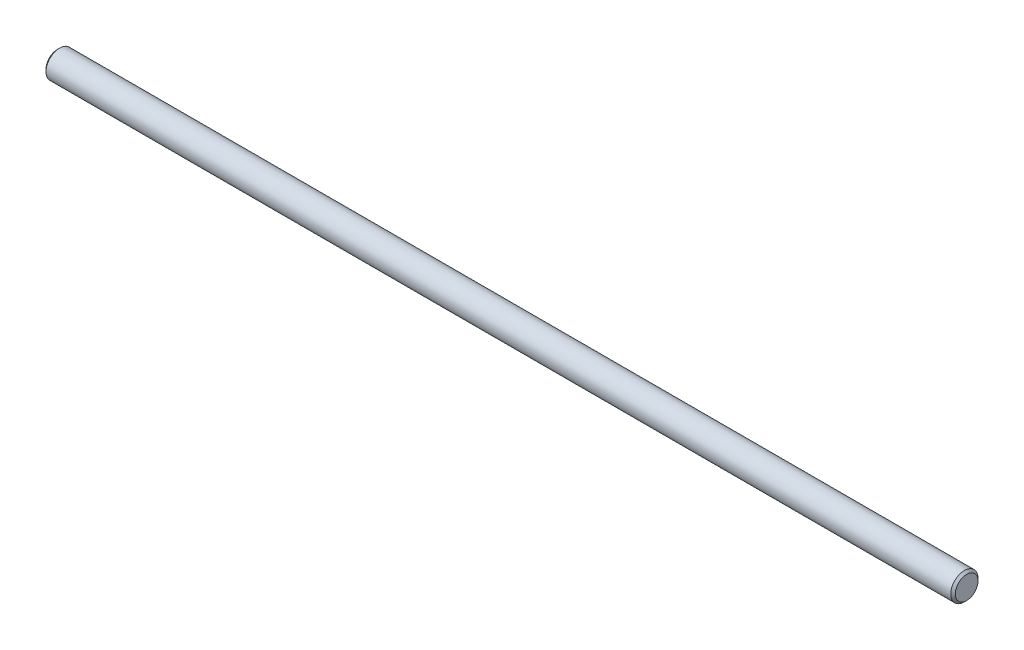
SolidWorks part; units mm, degrees
ref_plane "Front Plane" through (0, 0, 0) normal (0, 0, 1) x (1, 0, 0)
ref_plane "Top Plane" through (0, 0, 0) normal (0, 1, 0) x (1, 0, 0)
ref_plane "Right Plane" through (0, 0, 0) normal (1, 0, 0) x (0, 0, -1)
sketch "Sketch1" plane through (0, 0, 0) normal (0, 0, 1) x (1, 0, 0)
  line L0 (0, 0) -> (200, 0) construction
  line L1 (0, 0) -> (200, 0)
  line L2 (200, 0) -> (200, 3)
  line L3 (200, 3) -> (0, 3)
  line L4 (0, 3) -> (0, 0)
  dimension "L" = 200
  dimension "D" = 6
revolve "Revolve1" add sketch "Sketch1" angle 360 about L0
chamfer "Chamfer1" distance 0.5 angle 45 2 edges at (200, 0, 3) (0, 0, 3)
ref_plane "Plane1" through (0, 0, 3) normal (0, 0, 1) x (1, 0, 0)
ref_plane "Plane2" through (200, 0, 0) normal (1, 0, 0) x (0, 0, -1)
other "DeleteFace1" [suppressed]
chamfer "Chamfer2" [suppressed] distance 2 angle 45
ref_plane "Dim. KC" [suppressed] through (2, 0, 0) normal (1, 0, 0) x (0, 0, -1)
ref_plane "Plane3" [suppressed] through (2, 0, 0) normal (1, 0, 0) x (0, 0, -1)
ref_plane "Plane4" [suppressed] through (8, 0, 0) normal (1, 0, 0) x (0, 0, -1)
sketch "Sketch2" [suppressed] plane through (0, 0, 4) normal (0, 0, 1) x (1, 0, 0)
  line L0 (2, 0) -> (8, 0) construction
  line L1 (2, 1.5) -> (8, 1.5)
  line L2 (2, 1.5) -> (2, -1.5) construction
  line L3 (2, -1.5) -> (8, -1.5)
  line L4 (8, 1.5) -> (8, -1.5) construction
  line L5 (5, 1.5) -> (5, -1.5) construction
  line L6 (2, -4.4) -> (2, 4.4) construction
  line L7 (8, 1.5) -> (8, -1.5)
  line L8 (8, -4.4) -> (8, 4.4) construction
  line L9 (2, 1.5) -> (2, -1.5)
  line L12 (2, -4.4) -> (2, 4.4) construction
  dimension "A" = 6
  dimension "B_s" = 3
extrude "Boss-Extrude1" [suppressed] add sketch "Sketch2" against normal blind 1.8 separate body
fillet "Fillet1" [suppressed] type full round
fillet "Fillet2" [suppressed] type full round
sketch "Sketch3" [suppressed] plane through (0, 0, 4) normal (0, 0, 1) x (1, 0, 0)
  line L0 (9, 1.5) -> (9, -1.5) construction
  line L1 (6.5, 1.5) -> (11.5, 1.5)
  line L2 (6.5, 1.5) -> (6.5, -1.5)
  line L3 (6.5, -1.5) -> (11.5, -1.5)
  line L4 (11.5, 1.5) -> (11.5, -1.5)
  line L7 (6.5, 0) -> (11.5, 0) construction
  line L9 (10, 1.5) -> (10, -1.5) construction
  line L10 (8, 1.5) -> (8, -1.5) construction
  line L11 (2, 1.5) -> (8, 1.5) construction
  line L12 (2, -1.5) -> (8, -1.5) construction
  dimension "D1" = 1.5
  dimension "D2" = 2
  dimension "D3" = 1.5
extrude "Boss-Extrude2" [suppressed] add sketch "Sketch3" against normal blind 1.8
fillet "Fillet3" [suppressed] radius 0.1
other "DeleteFace2" [suppressed]
other "DeleteFace3" [suppressed]
combine bodies "Combine1" [suppressed] operation type subtract main body 101 bodies to subtract 146
ref_plane "KC_SEC1" [suppressed] through (5, 0, 0) normal (1, 0, 0) x (0, 0, -1)
ref_plane "KC_SEC2" [suppressed] through (9, 0, 0) normal (1, 0, 0) x (0, 0, -1)
ref_plane "Dim. WKC" [suppressed] through (2, 0, 0) normal (1, 0, 0) x (0, 0, -1)
ref_plane "Dim. K" [suppressed] through (20, 0, 0) normal (1, 0, 0) x (0, 0, -1)
ref_plane "Plane5" [suppressed] through (2, 0, 0) normal (1, 0, 0) x (0, 0, -1)
ref_plane "Plane6" [suppressed] through (20, 0, 0) normal (1, 0, 0) x (0, 0, -1)
sketch "Sketch4" [suppressed] plane through (0, 0, 4) normal (0, 0, 1) x (1, 0, 0)
  line L0 (2, 1.5) -> (2, -1.5)
  line L1 (2, 1.5) -> (8, 1.5)
  line L2 (2, 1.5) -> (2, -1.5) construction
  line L3 (2, -1.5) -> (8, -1.5)
  line L4 (8, 1.5) -> (8, -1.5)
  line L5 (2, -4.4) -> (2, 4.4) construction
  line L6 (2, -3.3) -> (2, 3.3) construction
  line L7 (8, 0) -> (2, 0) construction
  line L8 (5, 1.5) -> (5, -1.5) construction
  dimension "C" = 6
  dimension "B_s" = 3
extrude "Boss-Extrude3" [suppressed] add sketch "Sketch4" against normal blind 1.8 separate body
sketch "Sketch5" [suppressed] plane through (0, 0, 4) normal (0, 0, 1) x (1, 0, 0)
  line L0 (0, 0) -> (20, 0) construction
  line L2 (20, -3.3) -> (20, 3.3) construction
  line L4 (20, -3.3) -> (20, 3.3) construction
  line L5 (17, 1.5) -> (17, -1.5) construction
  line L9 (14, 1.5) -> (20, 1.5)
  line L10 (14, 1.5) -> (14, -1.5)
  line L11 (14, -1.5) -> (20, -1.5)
  line L12 (20, 1.5) -> (20, -1.5) construction
  line L13 (20, 1.5) -> (20, -1.5)
  dimension "B_s" = 3
  dimension "E" = 6
extrude "Boss-Extrude4" [suppressed] add sketch "Sketch5" against normal blind 1.8 separate body
sketch "Sketch6" [suppressed] plane through (0, 0, 4) normal (0, 0, 1) x (1, 0, 0)
  line L0 (2, 1.5) -> (8, 1.5) construction
  line L1 (6.5, 1.5) -> (11.5, 1.5)
  line L2 (6.5, 1.5) -> (6.5, -1.5)
  line L3 (6.5, -1.5) -> (11.5, -1.5)
  line L4 (11.5, 1.5) -> (11.5, -1.5)
  line L5 (2, -1.5) -> (8, -1.5) construction
  line L6 (8, 1.5) -> (8, -1.5) construction
  line L7 (9, 1.5) -> (9, -1.5) construction
  line L8 (10, 1.5) -> (10, -1.5) construction
  dimension "D1" = 1.5
  dimension "D2" = 2
  dimension "D3" = 1.5
extrude "Boss-Extrude5" [suppressed] add sketch "Sketch6" against normal blind 1.8
fillet "Fillet4" [suppressed] type full round
fillet "Fillet5" [suppressed] type full round
fillet "Fillet6" [suppressed] radius 0.1
fillet "Fillet7" [suppressed] type full round
fillet "Fillet8" [suppressed] type full round
fillet "Fillet9" [suppressed] radius 0.1
other "DeleteFace4" [suppressed]
other "DeleteFace5" [suppressed]
other "DeleteFace6" [suppressed]
other "DeleteFace7" [suppressed]
combine bodies "Combine2" [suppressed] operation type subtract main body 101 bodies to subtract 149 135
ref_plane "WKC_SEC1" [suppressed] through (5, 0, 0) normal (1, 0, 0) x (0, 0, -1)
ref_plane "WKC_SEC2" [suppressed] through (17, 0, 0) normal (1, 0, 0) x (0, 0, -1)
ref_plane "WKC_SEC3" [suppressed] through (9, 0, 0) normal (1, 0, 0) x (0, 0, -1)
ref_plane "Dim. KZ" [suppressed] through (2, 0, 0) normal (1, 0, 0) x (0, 0, -1)
ref_plane "Plane7" [suppressed] through (2, 0, 0) normal (1, 0, 0) x (0, 0, -1)
ref_plane "Plane8" [suppressed] through (8, 0, 0) normal (1, 0, 0) x (0, 0, -1)
sketch "Sketch7" [suppressed] plane through (0, 0, 4) normal (0, 0, 1) x (1, 0, 0)
  line L0 (0, 0) -> (8, 0) construction
  line L1 (2, 1.5) -> (8, 1.5)
  line L2 (2, 1.5) -> (2, -1.5) construction
  line L3 (2, -1.5) -> (8, -1.5)
  line L4 (8, 1.5) -> (8, -1.5) construction
  line L5 (2, -4.4) -> (2, 4.4) construction
  line L6 (2, -4.4) -> (2, 4.4) construction
  line L7 (2, 1.5) -> (2, -1.5)
  line L8 (8, 1.5) -> (8, -1.5)
  line L9 (8, -4.4) -> (8, 4.4) construction
  line L10 (5, 1.5) -> (5, -1.5) construction
  dimension "B_s" = 3
  dimension "Z" = 6
extrude "Boss-Extrude6" [suppressed] add sketch "Sketch7" against normal blind 1.8 separate body
fillet "Fillet10" [suppressed] type full round
fillet "Fillet11" [suppressed] type full round
sketch "Sketch8" [suppressed] plane through (0, 0, 4) normal (0, 0, 1) x (1, 0, 0)
  line L0 (1, 1.5) -> (1, -1.5) construction
  line L1 (-1.5, 1.5) -> (3.5, 1.5)
  line L2 (-1.5, 1.5) -> (-1.5, -1.5)
  line L3 (-1.5, -1.5) -> (3.5, -1.5)
  line L4 (3.5, 1.5) -> (3.5, -1.5)
  line L5 (2, 1.5) -> (2, -1.5) construction
  line L7 (-1.5, 0) -> (3.5, 0) construction
  line L9 (0, 1.5) -> (0, -1.5) construction
  line L10 (2, 1.5) -> (8, 1.5) construction
  line L11 (2, -1.5) -> (8, -1.5) construction
  dimension "D1" = 1.5
  dimension "D2" = 2
  dimension "D3" = 1.5
extrude "Boss-Extrude7" [suppressed] add sketch "Sketch8" against normal blind 1.8
fillet "Fillet12" [suppressed] radius 0.1
other "DeleteFace8" [suppressed]
other "DeleteFace9" [suppressed]
combine bodies "Combine3" [suppressed] operation type subtract main body 101 bodies to subtract 147
ref_plane "KZ_SEC1" [suppressed] through (5, 0, 0) normal (1, 0, 0) x (0, 0, -1)
ref_plane "KZ_SEC2" [suppressed] through (1, 0, 0) normal (1, 0, 0) x (0, 0, -1)
ref_plane "Dim. FC" [suppressed] through (1, 0, 0) normal (1, 0, 0) x (0, 0, -1)
sketch "Sketch9" [suppressed] plane through (0, 0, 0) normal (0, 1, 0) x (1, 0, 0)
  line L0 (0, 0) -> (2, 0) construction
  line L1 (1, -3) -> (2, -3)
  line L2 (1, -3) -> (1, -4)
  line L3 (1, -4) -> (2, -4)
  line L4 (2, -3) -> (2, -4)
  line L5 (1, -3.3) -> (1, 3.3) construction
  line L6 (1.5, -4) -> (1.5, -3) construction
  dimension "G" = 2
  dimension "H" = 1
  dimension "D" = 6
extrude "Cut-Extrude1" [suppressed] cut sketch "Sketch9" against normal through all and the other way through all
ref_plane "FC_SEC" [suppressed] through (1.5, 0, 0) normal (1, 0, 0) x (0, 0, -1)
ref_plane "Dim. WFC" [suppressed] through (1, 0, 0) normal (1, 0, 0) x (0, 0, -1)
ref_plane "Dim. W" [suppressed] through (19, 0, 0) normal (1, 0, 0) x (0, 0, -1)
sketch "Sketch10" [suppressed] plane through (0, 0, 0) normal (0, 1, 0) x (1, 0, 0)
  line L0 (0, 0) -> (19, 0) construction
  line L1 (1, -4) -> (2, -4)
  line L2 (1, -4) -> (1, -3)
  line L3 (1, -3) -> (2, -3)
  line L4 (2, -4) -> (2, -3)
  line L5 (1.5, -3) -> (1.5, -4) construction
  line L6 (19, -4) -> (18, -4)
  line L7 (19, -4) -> (19, -3)
  line L8 (19, -3) -> (18, -3)
  line L9 (18, -4) -> (18, -3)
  line L10 (1, -3.3) -> (1, 3.3) construction
  line L11 (19, -3.3) -> (19, 3.3) construction
  line L12 (18.5, -3) -> (18.5, -4) construction
  dimension "J" = 2
  dimension "V" = 2
  dimension "H" = 1
  dimension "D" = 6
  dimension "H_s_R" = 1
extrude "Cut-Extrude2" [suppressed] cut sketch "Sketch10" against normal through all and the other way through all
ref_plane "WFC_SEC1" [suppressed] through (1.5, 0, 0) normal (1, 0, 0) x (0, 0, -1)
ref_plane "WFC_SEC2" [suppressed] through (18.5, 0, 0) normal (1, 0, 0) x (0, 0, -1)
ref_plane "Dim. SFC" [suppressed] through (1, 0, 0) normal (1, 0, 0) x (0, 0, -1)
sketch "Sketch11" [suppressed] plane through (0, 0, 0) normal (0, 1, 0) x (1, 0, 0)
  line L0 (0, 0) -> (2, 0) construction
  line L1 (1, -4) -> (2, -4)
  line L2 (1, -4) -> (1, -3)
  line L3 (1, -3) -> (2, -3)
  line L4 (2, -4) -> (2, -3)
  line L5 (1, -3.3) -> (1, 3.3) construction
  line L6 (1.5, -3) -> (1.5, -4) construction
  dimension "SG" = 1
  dimension "H" = 1
  dimension "D" = 6
extrude "Cut-Extrude3" [suppressed] cut sketch "Sketch11" against normal through all and the other way through all
pattern_circular "CirPattern1" [suppressed] count 2 every 120 of bodies 119
ref_plane "Plane9" [suppressed] through (0, 0, 0) normal (0, -0.5, 0.866) x (1, 0, 0)
sketch "Sketch12" [suppressed] plane through (0, 0, 0) normal (0, -0.5, 0.866) x (1, 0, 0)
  line L0 (0, 0) -> (2, 0) construction
  line L2 (1, -3) -> (2, -3)
  line L3 (1, -3) -> (1, -4)
  line L4 (1, -4) -> (2, -4)
  line L5 (2, -3) -> (2, -4)
  line L6 (1, -3.3) -> (1, 3.3) construction
  dimension "D" = 6
  dimension "SG" = 1
  dimension "H" = 1
ref_plane "SFC_SEC" [suppressed] through (1.5, 0, 0) normal (1, 0, 0) x (0, 0, -1)
sketch "Sketch13" [suppressed] plane through (1.5, 0, 0) normal (1, 0, 0) x (0, 0, -1)
  line L0 (-4, 0) -> (-3, 0) construction
  line L1 (-3, 0) -> (-4, 0) construction
  line L2 (2, -3.4641) -> (1.5, -2.5981) construction
  line L3 (1.5, -2.5981) -> (2, -3.4641) construction
  line L4 (1.5, -2.5981) -> (2, -3.4641) construction
  dimension "ANG" = 120
sketch "Sketch14" [suppressed] plane through (0, 0, 0) normal (0, 1, 0) x (1, 0, 0)
  line L0 (0, 0) -> (20, 0) construction
  line L1 (1.5, 4) -> (1.5, 3.5) construction
  line L2 (0, 3.5) -> (3, 3.5)
  line L3 (0, 3.5) -> (0, 4)
  line L4 (0, 4) -> (3, 4)
  line L5 (3, 3.5) -> (3, 4)
  line L6 (17, 3.5) -> (20, 3.5)
  line L7 (17, 3.5) -> (17, 4)
  line L8 (17, 4) -> (20, 4)
  line L9 (20, 3.5) -> (20, 4)
  line L10 (0, -4) -> (3, -4)
  line L11 (0, -4) -> (0, -3.5)
  line L12 (0, -3.5) -> (3, -3.5)
  line L13 (3, -4) -> (3, -3.5)
  line L14 (17, -4) -> (20, -4)
  line L15 (17, -4) -> (17, -3.5)
  line L16 (17, -3.5) -> (20, -3.5)
  line L17 (20, -4) -> (20, -3.5)
  line L18 (1.5, -3.5) -> (1.5, -4) construction
  line L19 (18.5, 4) -> (18.5, 3.5) construction
  line L20 (18.5, -3.5) -> (18.5, -4) construction
  dimension "D" = 6
  dimension "W_1" = 4
  dimension "KWC" = 3
  dimension "KWC_L1" = 3
  dimension "KWC_R1" = 3
  dimension "KWC_R2" = 3
  dimension "W_1_R" = 7
extrude "Cut-Extrude4" [suppressed] cut sketch "Sketch14" against normal through all and the other way through all
ref_plane "KWC_SEC1" [suppressed] through (1.5, 0, 0) normal (1, 0, 0) x (0, 0, -1)
ref_plane "KWC_SEC2" [suppressed] through (18.5, 0, 0) normal (1, 0, 0) x (0, 0, -1)
sketch "Sketch15" [suppressed] plane through (0, 0, 0) normal (0, 1, 0) x (1, 0, 0)
  line L0 (0, 0) -> (20, 0) construction
  line L1 (1.5, -3) -> (1.5, -4) construction
  line L2 (0, 3) -> (3, 3)
  line L3 (0, 3) -> (0, 4)
  line L4 (0, 4) -> (3, 4)
  line L5 (3, 3) -> (3, 4)
  line L6 (17, 3) -> (20, 3)
  line L7 (17, 3) -> (17, 4)
  line L8 (17, 4) -> (20, 4)
  line L9 (20, 3) -> (20, 4)
  line L10 (0, -4) -> (3, -4)
  line L11 (0, -4) -> (0, -3)
  line L12 (0, -3) -> (3, -3)
  line L13 (3, -4) -> (3, -3)
  line L14 (17, -4) -> (20, -4)
  line L15 (17, -4) -> (17, -3)
  line L16 (17, -3) -> (20, -3)
  line L17 (20, -4) -> (20, -3)
  line L18 (18.5, -3) -> (18.5, -4) construction
  dimension "D" = 6
  dimension "KWC_L1" = 3
  dimension "KWC_R1" = 3
  dimension "WC" = 6
  dimension "KWC" = 3
  dimension "KWC_R2" = 3
  dimension "WC_R" = 6
extrude "Cut-Extrude5" [suppressed] cut sketch "Sketch15" against normal through all and the other way through all
ref_plane "WC_SEC1" [suppressed] through (1.5, 0, 0) normal (1, 0, 0) x (0, 0, -1)
ref_plane "WC_SEC2" [suppressed] through (18.5, 0, 0) normal (1, 0, 0) x (0, 0, -1)
sketch "Sketch16" [suppressed] plane through (0, 0, 0) normal (0, 0, 1) x (1, 0, 0)
  line L0 (20, 4) -> (0, 4) construction
  line L1 (1.1, 3.5) -> (2, 3.5)
  line L2 (1.1, 3.5) -> (1.1, 4)
  line L3 (1.1, 4) -> (2, 4)
  line L4 (2, 3.5) -> (2, 4)
  line L5 (0, 0) -> (2, 0) construction
  line L6 (0, 4) -> (0, 0) construction
  dimension "D_s_1" = 7
  dimension "M_s" = 0.9
  dimension "TA" = 6
revolve "Cut-Revolve1" [suppressed] cut sketch "Sketch16" angle 360 about L5
sketch "Sketch17" [suppressed] plane through (0, 0, 0) normal (0, 0, 1) x (1, 0, 0)
  line L1 (18, 3.5) -> (18.9, 3.5)
  line L2 (18, 3.5) -> (18, 4)
  line L3 (18, 4) -> (18.9, 4)
  line L4 (18.9, 3.5) -> (18.9, 4)
  line L5 (0, 0) -> (20, 0) construction
  line L7 (20, -3.3) -> (20, 3.3) construction
  dimension "D_s_1" = 7
  dimension "M_s" = 0.9
  dimension "D" = 6
  dimension "TB" = 6
revolve "Cut-Revolve2" [suppressed] cut sketch "Sketch17" angle 360 about L5
sketch "Sketch18" [suppressed] plane through (0, 0, 0) normal (0, 0, 1) x (1, 0, 0)
  line L0 (0, 0) -> (20, 0) construction
  line L1 (0, 4) -> (0, -4) construction
  line L3 (1, 4) -> (5, 4)
  line L4 (1, 4) -> (1, 3.5)
  line L5 (1, 3.5) -> (5, 3.5)
  line L6 (5, 4) -> (5, 3.5)
  line L7 (20, 4) -> (0, 4) construction
  line L8 (20, -3.3) -> (20, 3.3) construction
  dimension "D_s_2" = 7
  dimension "UC" = 1
  dimension "L1_s" = 4
revolve "Cut-Revolve3" [suppressed] cut sketch "Sketch18" angle 360 about L0
ref_plane "Dim. SC" [suppressed] through (2, 0, 0) normal (1, 0, 0) x (0, 0, -1)
sketch "Sketch19" [suppressed] plane through (0, 0, 0) normal (0, 1, 0) x (1, 0, 0)
  line L0 (20, -3.3) -> (20, 3.3) construction
  line L1 (2, -3.5) -> (10, -3.5)
  line L2 (2, -3.5) -> (2, -4)
  line L3 (2, -4) -> (10, -4)
  line L4 (10, -3.5) -> (10, -4)
  line L5 (2, 4) -> (10, 4)
  line L6 (2, 4) -> (2, 3.5)
  line L7 (2, 3.5) -> (10, 3.5)
  line L8 (10, 4) -> (10, 3.5)
  line L9 (6, 4) -> (6, 3.5) construction
  line L10 (6, -3.5) -> (6, -4) construction
  line L12 (0, 0) -> (20, 0) construction
  line L14 (2, -3.3) -> (2, 3.3) construction
  dimension "W_2" = 4
  dimension "L2_s" = 8
  dimension "D" = 6
  dimension "L2_s_L1" = 8
extrude "Cut-Extrude6" [suppressed] cut sketch "Sketch19" against normal through all and the other way through all
ref_plane "SC_SEC" [suppressed] through (6, 0, 0) normal (1, 0, 0) x (0, 0, -1)
equation "\"Plane dim\"= \"D@Sketch1\" * 0.5"
equation "\"D1@Plane3\"= if ( \"KC@Dim. KC\" < 1 , 0 , \"KC@Dim. KC\" )"
equation "\"D1@Plane4\" = if ( \"KC@Dim. KC\" > \"L@Sketch1\" - \"A@Sketch2\" - 1 , \"L@Sketch1\" , \"KC@Dim. KC\" + \"A@Sketch2\" )"
equation "\"D1@Plane5\"=if ( \"WKC@Dim. WKC\" < 1 , 0 , \"WKC@Dim. WKC\" )"
equation "\"D1@Plane6\"=if ( \"K@Dim. K\" < 1 , 0 , \"K@Dim. K\" )"
equation "\"D1@Plane7\"=if ( \"KZ@Dim. KZ\" < 1 , 0 , \"KZ@Dim. KZ\" )"
equation "\"D1@Plane8\"=if ( \"KZ@Dim. KZ\" > \"L@Sketch1\" - \"Z@Sketch7\" - 1 , \"L@Sketch1\", \"KZ@Dim. KZ\" + \"Z@Sketch7\" )"
equation "\"D1@Sketch3\"=\"B_s@Sketch2\"/2"
equation "\"D3@Sketch3\"=\"B_s@Sketch2\"/2"
equation "\"D1@Sketch8\"=\"B_s@Sketch7\"/2"
equation "\"D3@Sketch8\"=\"B_s@Sketch7\"/2"
equation "\"D1@Sketch6\"=\"B_s@Sketch4\"/2"
equation "\"D3@Sketch6\"=\"B_s@Sketch4\"/2"
equation "\"D@Sketch12\" = \"D@Sketch11\""
equation "\"SG@Sketch12\" = \"SG@Sketch11\""
equation "\"H@Sketch12\"= \"H@Sketch11\""
